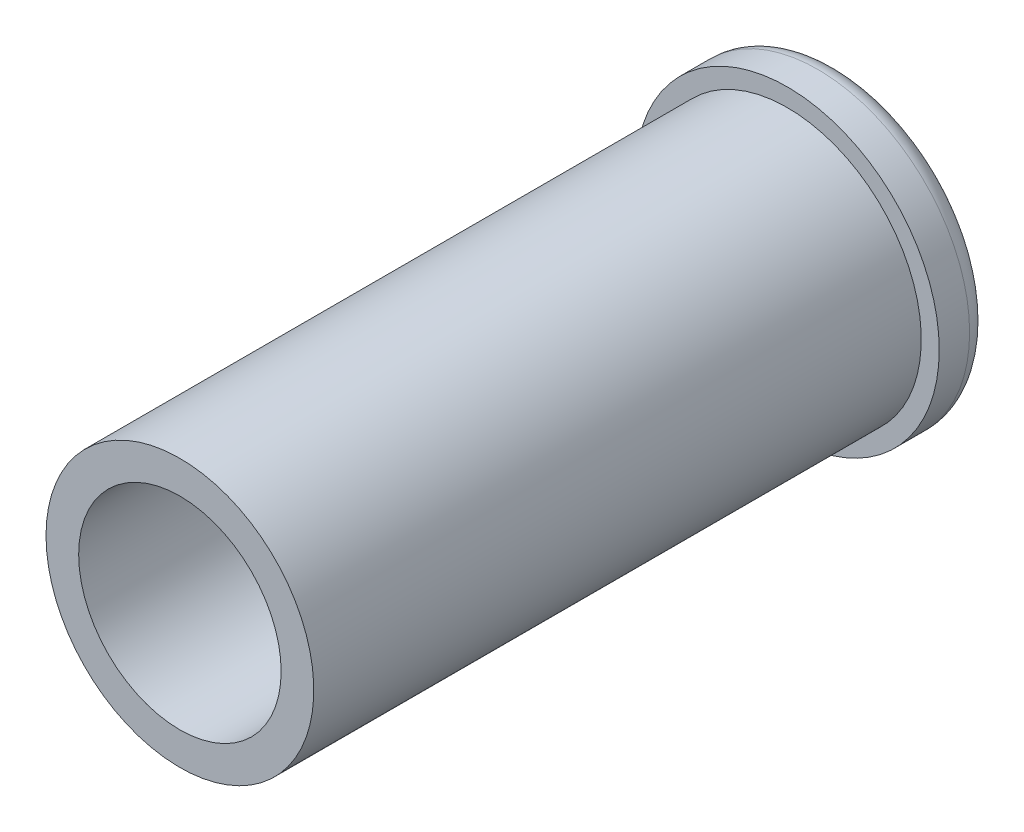
SolidWorks part; units mm, degrees
material "AISI 4130 Steel, annealed at 865C"
ref_plane "Front Plane" through (0, 0, 0) normal (0, 0, 1) x (1, 0, 0)
ref_plane "Top Plane" through (0, 0, 0) normal (0, 1, 0) x (1, 0, 0)
ref_plane "Right Plane" through (0, 0, 0) normal (1, 0, 0) x (0, 0, -1)
sketch3d "3DSketch1"
  circle A1 centre (0, 0, 25.4) radius 8.525 construction
  circle A3 centre (0, 0, 25.4) radius 9.525 construction
  point P4 (0, 0, 33.925)
  point P8 (0, 0, 34.925)
ref_plane "Plane1" through (0, 0, 25.4) normal (0, 0, 1) x (1, 0, 0)
sketch "Sketch2" plane through (0, 0, 25.4) normal (0, 0, 1) x (1, 0, 0)
  circle A0 centre (0, 0) radius 8.398
  circle A1 centre (0, 0) radius 8.525 construction
  circle A2 centre (0, 0) radius 9.525
  dimension "D1" = 0.127
  dimension "D2" = 19.05
extrude "Boss-Extrude3" add sketch "Sketch2" along normal blind 38.1 contours A0 region at (0, 0, 25.4)
extrude "Boss-Extrude4" add sketch "Sketch2<3>" against normal blind 3.175 separate body contours A0 | A2 A0 | A0 | A2 region at (0, 0, 25.4) region at (-9.2556, 0, 25.4)
sketch "Sketch2<3>" plane through (0, 0, 25.4) normal (0, 0, 1) x (1, 0, 0) same geometry as "Sketch2"
sketch "Sketch3" plane through (0, 0, 25.4) normal (0, 0, 1) x (1, 0, 0)
  circle A0 centre (0, 0) radius 6.35
  dimension "D1" = 12.7
extrude "Cut-Extrude1" cut sketch "Sketch3" against normal through all both and the other way through all
combine bodies "Combine1" operation type add bodies to combine 106 105
fillet "Fillet1" radius 1.27 2 edges at (9.525, 0, 22.225) (6.35, 0, 22.225)
